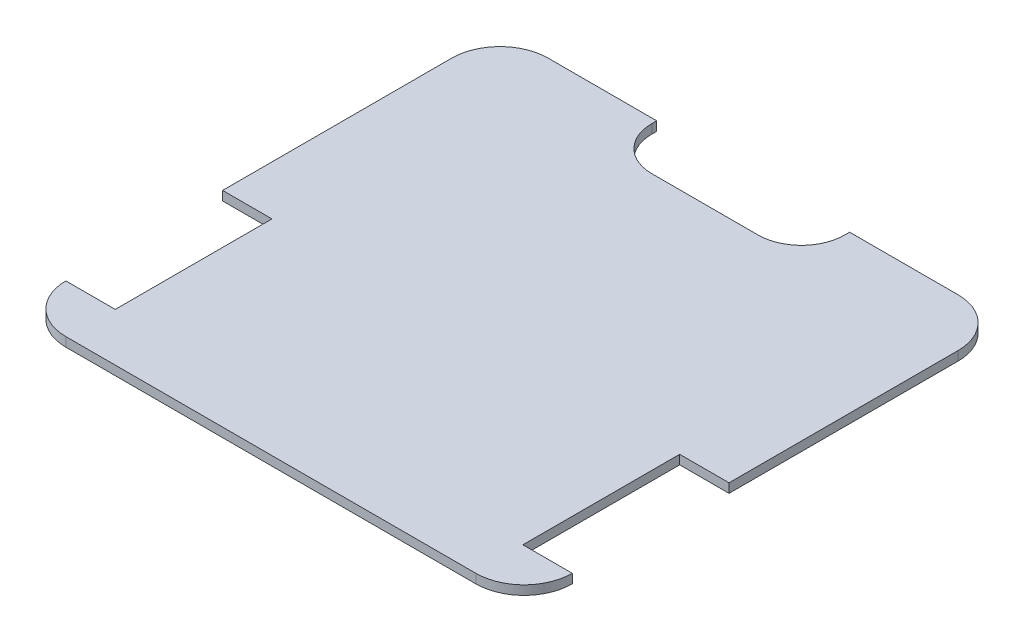
SolidWorks part; units mm, degrees
ref_plane "Front Plane" through (0, 0, 0) normal (0, 0, 1) x (1, 0, 0)
ref_plane "Top Plane" through (0, 0, 0) normal (0, 1, 0) x (1, 0, 0)
ref_plane "Right Plane" through (0, 0, 0) normal (1, 0, 0) x (0, 0, -1)
sketch "Sketch1" plane through (0, 0, 0) normal (0, 1, 0) x (1, 0, 0)
  line L1 (-133.35, 127) -> (133.35, 127)
  line L2 (-133.35, 127) -> (-133.35, -127)
  line L3 (-133.35, -127) -> (133.35, -127)
  line L4 (133.35, 127) -> (133.35, -127)
  line L5 (-133.35, 127) -> (133.35, -127) construction
  line L6 (-133.35, -127) -> (133.35, 127) construction
  point P0 (0, 0)
  dimension "D1" = 266.7
  dimension "D2" = 254
extrude "Boss-Extrude1" add sketch "Sketch1" along normal blind 4.826
sketch "Sketch2" plane through (0, 4.826, 0) normal (0, 1, 0) x (1, 0, 0)
  line L0 (-133.35, 127) -> (-133.35, -127) construction
  line L1 (-133.35, -19.05) -> (-107.35, -19.05)
  line L2 (-133.35, -19.05) -> (-133.35, -101.6)
  line L3 (-133.35, -101.6) -> (-107.35, -101.6)
  line L4 (-107.35, -19.05) -> (-107.35, -101.6)
  line L5 (133.35, -127) -> (133.35, 127) construction
  line L6 (133.35, -19.05) -> (107.35, -19.05)
  line L7 (133.35, -19.05) -> (133.35, -101.6)
  line L8 (133.35, -101.6) -> (107.35, -101.6)
  line L9 (107.35, -19.05) -> (107.35, -101.6)
  line L10 (-133.35, -127) -> (133.35, -127) construction
  dimension "D1" = 25.4
  dimension "D2" = 25.4
  dimension "D3" = 82.55
  dimension "D4" = 82.55
  dimension "D5" = 26
  dimension "D6" = 26
extrude "Cut-Extrude1" cut sketch "Sketch2" against normal blind 4.826
sketch "Sketch4" plane through (0, 4.826, 0) normal (0, 1, 0) x (1, 0, 0)
  line L0 (0, -127) -> (0, 127) construction
  line L1 (-133.35, -127) -> (133.35, -127) construction
  line L2 (133.35, 127) -> (-133.35, 127) construction
  line L3 (-133.35, 101.6) -> (-107.95, 101.6) construction
  line L4 (-133.35, 127) -> (-133.35, -19.05) construction
  line L5 (-107.95, 101.6) -> (-107.95, 127) construction
  line L6 (-133.35, 101.6) -> (-133.35, 127)
  line L7 (-133.35, 127) -> (-107.95, 127)
  line L8 (133.35, 101.6) -> (133.35, 127)
  line L9 (133.35, 127) -> (107.95, 127)
  arc A0 (-133.35, 101.6) -> (-107.95, 127) centre (-107.95, 101.6) cw
  arc A1 (133.35, 101.6) -> (107.95, 127) centre (107.95, 101.6) ccw
extrude "Cut-Extrude3" cut sketch "Sketch4" against normal blind 4.826
sketch "Sketch7" plane through (0, 4.826, 0) normal (0, 1, 0) x (1, 0, 0)
  line L0 (0, -127) -> (0, 127) construction
  line L1 (-133.35, -127) -> (133.35, -127) construction
  line L2 (107.95, 127) -> (-107.95, 127) construction
  line L3 (50.8, 101.6) -> (50.8, 127)
  line L4 (50.8, 101.6) -> (-50.8, 101.6)
  line L5 (0, 101.6) -> (0, 127)
  line L6 (50.8, 127) -> (-50.8, 127)
  line L7 (-50.8, 101.6) -> (-50.8, 127)
  line M6 (107.95, 127) -> (-107.95, 127)
  dimension "D2" = 50.8
extrude "Cut-Extrude5" cut sketch "Sketch7" against normal blind 4.826 contours L7 L4 L5 M6 | L5 L4 L3 M6 region at (25.4, 4.826, -114.3) region at (-25.4, 4.826, -114.3)
fillet "Fillet9" radius 22.86 1 edges at (-50.8, 2.413, -101.6) type face fillet first side face at (0, 2.413, -101.6) second side face at (-50.8, 2.413, -114.3)
fillet "Fillet10" radius 22.86 1 edges at (50.8, 2.413, -101.6) type face fillet first side face at (11.43, 2.413, -101.6) second side face at (50.8, 2.413, -114.3)
sketch "Sketch8" plane through (0, 4.826, 0) normal (0, 1, 0) x (1, 0, 0)
  line L0 (-133.35, -101.6) -> (-107.95, -101.6) construction
  line L1 (-107.95, -101.6) -> (-107.95, -127) construction
  line L2 (-133.35, -127) -> (133.35, -127) construction
  line L3 (-133.35, -101.6) -> (-133.35, -127)
  line L4 (-133.35, -127) -> (-107.95, -127)
  line L5 (0, -127) -> (0, 101.6) construction
  line L6 (27.94, 101.6) -> (-27.94, 101.6) construction
  line L7 (133.35, -127) -> (107.95, -127)
  line L8 (133.35, -101.6) -> (133.35, -127)
  arc A0 (-133.35, -101.6) -> (-107.95, -127) centre (-107.95, -101.6) ccw
  arc A1 (133.35, -101.6) -> (107.95, -127) centre (107.95, -101.6) cw
extrude "Cut-Extrude6" cut sketch "Sketch8" against normal blind 4.826
equation "\"MDF\"= 0.19in"
equation "\"GenDiameter\"= 60mm"
equation "\"GenCutDiameter\" = 1.8in"
equation "\"GenCutDistance\" = 1"
equation "\"TowerHeight\" = 6in"
equation "\"TowerFrontBase\" = 3in"
equation "\"FunnelHeight\" = 1in"
equation "\"FunnelAngle\" = 20"
equation "\"TowerSideBase\" = 3in"
equation "\"BaseLength\" = 10in"
equation "\"BaseWidth\" = 10.5in"
equation "\"WheelHoleLength\" = 3.25in"
equation "\"WheelHoleWidth\" = 26mm"
equation "\"DropLength\" = 1in"
equation "\"D1@Sketch1\"=\"BaseWidth\""
equation "\"D2@Sketch1\"=\"BaseLength\""
equation "\"D1@Boss-Extrude1\"=\"MDF\""
equation "\"WheelHoleFromBack\" = 1in"
equation "\"D1@Sketch2\"=\"WheelHoleFromBack\""
equation "\"D2@Sketch2\"=\"WheelHoleFromBack\""
equation "\"D3@Sketch2\"=\"WheelHoleLength\""
equation "\"D4@Sketch2\"=\"WheelHoleLength\""
equation "\"D5@Sketch2\"=\"WheelHoleWidth\""
equation "\"D6@Sketch2\"=\"WheelHoleWidth\""
equation "\"D1@Cut-Extrude1\"=\"MDF\""
equation "\"DropWidth\" = 8.5in"
equation "\"BumperWidth\" = 1in"
equation "\"D1@Sketch4\"=\"BumperWidth\""
equation "\"D2@Sketch4\"=\"WheelHoleFromBack\""
equation "\"D1@Cut-Extrude3\"=\"MDF\""
equation "\"D1@Sketch7\"=\"DropLength\""
equation "\"D2@Sketch7\"=\"DropWidthTop\"/2"
equation "\"D1@Cut-Extrude5\"=\"MDF\""
equation "\"D1@Sketch8\"=\"BumperWidth\""
equation "\"D1@Cut-Extrude6\"=\"MDF\""
equation "\"DropWidthTop\" = 4in"
